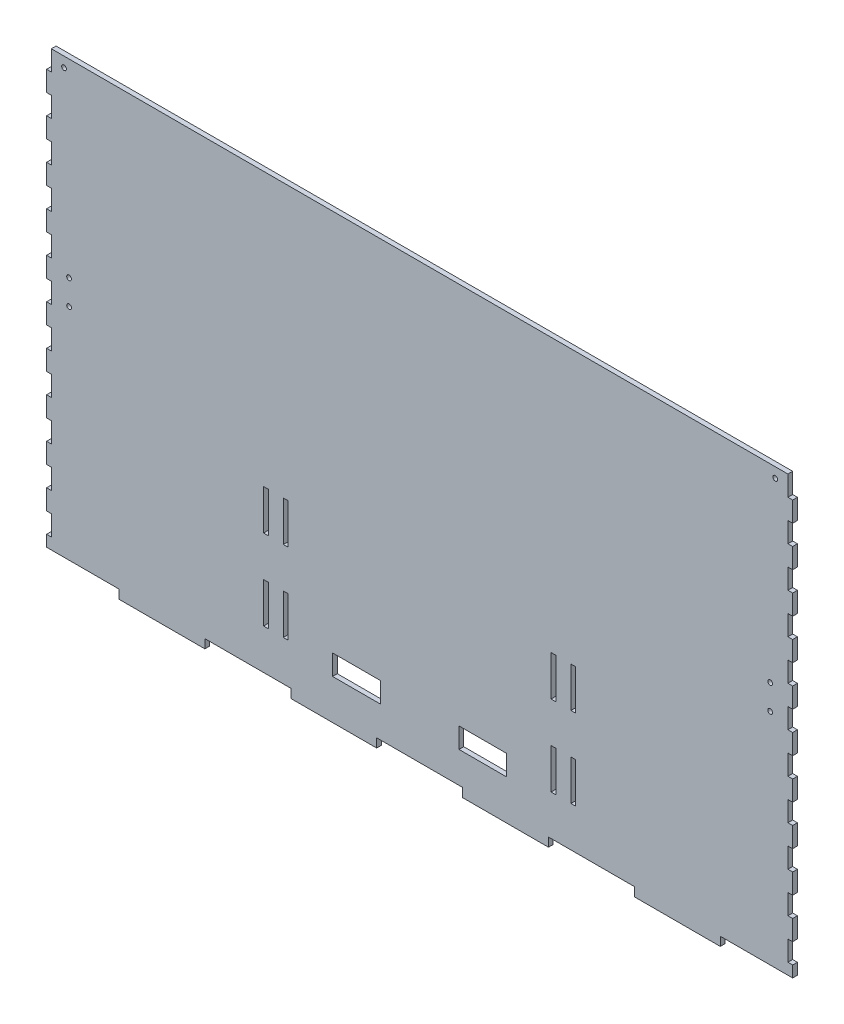
SolidWorks part; units mm, degrees
ref_plane "Front Plane" through (0, 0, 0) normal (0, 0, 1) x (1, 0, 0)
ref_plane "Top Plane" through (0, 0, 0) normal (0, 1, 0) x (1, 0, 0)
ref_plane "Right Plane" through (0, 0, 0) normal (1, 0, 0) x (0, 0, -1)
sketch "Sketch1" plane through (0, 0, 0) normal (0, 0, 1) x (1, 0, 0)
  line L0 (0, 139.7) -> (0, -139.7) construction
  line L1 (-406.4, 139.7) -> (406.4, 139.7)
  line L2 (-406.4, 139.7) -> (-406.4, -139.7)
  line L3 (-406.4, -139.7) -> (406.4, -139.7)
  line L4 (406.4, 139.7) -> (406.4, -139.7)
  line L49 (-380.8222, 127) -> (-380.8222, 114.3)
  line L54 (-380.8222, 139.7) -> (-377.825, 139.7)
  line L55 (-380.8222, 139.7) -> (-380.8222, 127)
  line L56 (-380.8222, 127) -> (-377.825, 127)
  line L57 (-377.825, 139.7) -> (-377.825, 127)
  line L58 (-380.8222, 127) -> (-377.825, 127)
  line L59 (-377.825, 127) -> (-377.825, 114.3)
  line L60 (-380.8222, 114.3) -> (-377.825, 114.3)
  line L61 (-380.8222, 114.3) -> (-380.8222, 101.6)
  line L62 (-380.8222, 114.3) -> (-377.825, 114.3)
  line L63 (-377.825, 114.3) -> (-377.825, 101.6)
  line L64 (-380.8222, 101.6) -> (-377.825, 101.6)
  line L65 (-380.8222, 101.6) -> (-380.8222, 88.9)
  line L66 (-380.8222, 101.6) -> (-377.825, 101.6)
  line L67 (-377.825, 101.6) -> (-377.825, 88.9)
  line L68 (-380.8222, 88.9) -> (-377.825, 88.9)
  line L69 (-380.8222, 88.9) -> (-380.8222, 76.2)
  line L70 (-380.8222, 88.9) -> (-377.825, 88.9)
  line L71 (-377.825, 88.9) -> (-377.825, 76.2)
  line L72 (-380.8222, 76.2) -> (-377.825, 76.2)
  line L73 (-380.8222, 76.2) -> (-380.8222, 63.5)
  line L74 (-380.8222, 76.2) -> (-377.825, 76.2)
  line L75 (-377.825, 76.2) -> (-377.825, 63.5)
  line L76 (-380.8222, 63.5) -> (-377.825, 63.5)
  line L77 (-380.8222, 63.5) -> (-380.8222, 50.8)
  line L78 (-380.8222, 63.5) -> (-377.825, 63.5)
  line L79 (-377.825, 63.5) -> (-377.825, 50.8)
  line L80 (-380.8222, 50.8) -> (-377.825, 50.8)
  line L81 (-380.8222, 50.8) -> (-380.8222, 38.1)
  line L82 (-380.8222, 50.8) -> (-377.825, 50.8)
  line L83 (-377.825, 50.8) -> (-377.825, 38.1)
  line L84 (-380.8222, 38.1) -> (-377.825, 38.1)
  line L85 (-380.8222, 38.1) -> (-380.8222, 25.4)
  line L86 (-380.8222, 38.1) -> (-377.825, 38.1)
  line L87 (-377.825, 38.1) -> (-377.825, 25.4)
  line L88 (-380.8222, 25.4) -> (-377.825, 25.4)
  line L89 (377.825, 127) -> (377.825, 114.3)
  line L90 (377.825, 139.7) -> (380.8222, 139.7)
  line L91 (377.825, 139.7) -> (377.825, 127)
  line L92 (377.825, 127) -> (380.8222, 127)
  line L93 (380.8222, 139.7) -> (380.8222, 127)
  line L94 (377.825, 127) -> (380.8222, 127)
  line L95 (380.8222, 127) -> (380.8222, 114.3)
  line L96 (377.825, 114.3) -> (380.8222, 114.3)
  line L97 (377.825, 114.3) -> (377.825, 101.6)
  line L98 (377.825, 114.3) -> (380.8222, 114.3)
  line L99 (380.8222, 114.3) -> (380.8222, 101.6)
  line L100 (377.825, 101.6) -> (380.8222, 101.6)
  line L101 (377.825, 101.6) -> (377.825, 88.9)
  line L102 (377.825, 101.6) -> (380.8222, 101.6)
  line L103 (380.8222, 101.6) -> (380.8222, 88.9)
  line L104 (377.825, 88.9) -> (380.8222, 88.9)
  line L105 (377.825, 88.9) -> (377.825, 76.2)
  line L106 (377.825, 88.9) -> (380.8222, 88.9)
  line L107 (380.8222, 88.9) -> (380.8222, 76.2)
  line L108 (377.825, 76.2) -> (380.8222, 76.2)
  line L109 (377.825, 76.2) -> (377.825, 63.5)
  line L110 (377.825, 76.2) -> (380.8222, 76.2)
  line L111 (380.8222, 76.2) -> (380.8222, 63.5)
  line L112 (377.825, 63.5) -> (380.8222, 63.5)
  line L113 (377.825, 63.5) -> (377.825, 50.8)
  line L114 (377.825, 63.5) -> (380.8222, 63.5)
  line L115 (380.8222, 63.5) -> (380.8222, 50.8)
  line L116 (377.825, 50.8) -> (380.8222, 50.8)
  line L117 (377.825, 50.8) -> (377.825, 38.1)
  line L118 (377.825, 50.8) -> (380.8222, 50.8)
  line L119 (380.8222, 50.8) -> (380.8222, 38.1)
  line L120 (377.825, 38.1) -> (380.8222, 38.1)
  line L121 (377.825, 38.1) -> (377.825, 25.4)
  line L122 (377.825, 38.1) -> (380.8222, 38.1)
  line L123 (380.8222, 38.1) -> (380.8222, 25.4)
  line L124 (377.825, 25.4) -> (380.8222, 25.4)
  line L125 (-352.2133, -134.112) -> (-352.2133, -139.7)
  line L126 (-406.4, -134.112) -> (-352.2133, -134.112)
  line L127 (-406.4, -134.112) -> (-406.4, -139.7)
  line L128 (-406.4, -139.7) -> (-352.2133, -139.7)
  line L129 (-352.2133, -134.112) -> (-352.2133, -139.7)
  line L130 (-352.2133, -134.112) -> (-298.0267, -134.112)
  line L131 (-298.0267, -134.112) -> (-298.0267, -139.7)
  line L132 (-352.2133, -139.7) -> (-298.0267, -139.7)
  line L133 (-298.0267, -134.112) -> (-298.0267, -139.7)
  line L134 (-298.0267, -134.112) -> (-243.84, -134.112)
  line L135 (-243.84, -134.112) -> (-243.84, -139.7)
  line L136 (-298.0267, -139.7) -> (-243.84, -139.7)
  line L137 (-243.84, -134.112) -> (-243.84, -139.7)
  line L138 (-243.84, -134.112) -> (-189.6533, -134.112)
  line L139 (-189.6533, -134.112) -> (-189.6533, -139.7)
  line L140 (-243.84, -139.7) -> (-189.6533, -139.7)
  line L141 (-189.6533, -134.112) -> (-189.6533, -139.7)
  line L142 (-189.6533, -134.112) -> (-135.4667, -134.112)
  line L143 (-135.4667, -134.112) -> (-135.4667, -139.7)
  line L144 (-189.6533, -139.7) -> (-135.4667, -139.7)
  line L145 (-135.4667, -134.112) -> (-135.4667, -139.7)
  line L146 (-135.4667, -134.112) -> (-81.28, -134.112)
  line L147 (-81.28, -134.112) -> (-81.28, -139.7)
  line L148 (-135.4667, -139.7) -> (-81.28, -139.7)
  line L149 (-81.28, -134.112) -> (-81.28, -139.7)
  line L150 (-81.28, -134.112) -> (-27.0933, -134.112)
  line L151 (-27.0933, -134.112) -> (-27.0933, -139.7)
  line L152 (-81.28, -139.7) -> (-27.0933, -139.7)
  line L153 (-27.0933, -134.112) -> (-27.0933, -139.7)
  line L154 (-27.0933, -134.112) -> (27.0933, -134.112)
  line L155 (27.0933, -134.112) -> (27.0933, -139.7)
  line L156 (-27.0933, -139.7) -> (27.0933, -139.7)
  line L157 (27.0933, -134.112) -> (27.0933, -139.7)
  line L158 (27.0933, -134.112) -> (81.28, -134.112)
  line L159 (81.28, -134.112) -> (81.28, -139.7)
  line L160 (27.0933, -139.7) -> (81.28, -139.7)
  line L161 (81.28, -134.112) -> (81.28, -139.7)
  line L162 (81.28, -134.112) -> (135.4667, -134.112)
  line L163 (135.4667, -134.112) -> (135.4667, -139.7)
  line L164 (81.28, -139.7) -> (135.4667, -139.7)
  line L165 (135.4667, -134.112) -> (135.4667, -139.7)
  line L166 (135.4667, -134.112) -> (189.6533, -134.112)
  line L167 (189.6533, -134.112) -> (189.6533, -139.7)
  line L168 (135.4667, -139.7) -> (189.6533, -139.7)
  line L169 (189.6533, -134.112) -> (189.6533, -139.7)
  line L170 (189.6533, -134.112) -> (243.84, -134.112)
  line L171 (243.84, -134.112) -> (243.84, -139.7)
  line L172 (189.6533, -139.7) -> (243.84, -139.7)
  line L173 (243.84, -134.112) -> (243.84, -139.7)
  line L174 (243.84, -134.112) -> (298.0267, -134.112)
  line L175 (298.0267, -134.112) -> (298.0267, -139.7)
  line L176 (243.84, -139.7) -> (298.0267, -139.7)
  line L177 (298.0267, -134.112) -> (298.0267, -139.7)
  line L178 (298.0267, -134.112) -> (352.2133, -134.112)
  line L179 (352.2133, -134.112) -> (352.2133, -139.7)
  line L180 (298.0267, -139.7) -> (352.2133, -139.7)
  line L181 (352.2133, -134.112) -> (352.2133, -139.7)
  line L182 (352.2133, -134.112) -> (406.4, -134.112)
  line L183 (406.4, -134.112) -> (406.4, -139.7)
  line L184 (352.2133, -139.7) -> (406.4, -139.7)
  line L205 (-90.678, 84.5227) -> (-90.678, -139.7) construction
  line L206 (90.678, 84.5227) -> (90.678, -139.7) construction
  line L207 (-90.678, -27.5886) -> (90.678, -27.5886) construction
  line L208 (-380.8222, 25.4) -> (-380.8222, 12.7)
  line L209 (-380.8222, 25.4) -> (-377.825, 25.4)
  line L210 (-377.825, 25.4) -> (-377.825, 12.7)
  line L211 (-380.8222, 12.7) -> (-377.825, 12.7)
  line L212 (-380.8222, 12.7) -> (-380.8222, 0)
  line L213 (-380.8222, 12.7) -> (-377.825, 12.7)
  line L214 (-377.825, 12.7) -> (-377.825, 0)
  line L215 (-380.8222, 0) -> (-377.825, 0)
  line L224 (-377.825, 0) -> (377.825, 0) construction
  line L229 (377.825, 25.4) -> (377.825, 12.7)
  line L230 (377.825, 25.4) -> (380.8222, 25.4)
  line L231 (380.8222, 25.4) -> (380.8222, 12.7)
  line L232 (377.825, 12.7) -> (380.8222, 12.7)
  line L233 (377.825, 12.7) -> (377.825, 0)
  line L234 (377.825, 12.7) -> (380.8222, 12.7)
  line L235 (380.8222, 12.7) -> (380.8222, 0)
  line L236 (377.825, 0) -> (380.8222, 0)
  line L237 (-380.8222, 0) -> (-380.8222, -12.7)
  line L238 (-380.8222, 0) -> (-377.825, 0)
  line L239 (-377.825, 0) -> (-377.825, -12.7)
  line L240 (-380.8222, -12.7) -> (-377.825, -12.7)
  line L241 (-380.8222, -12.7) -> (-380.8222, -25.4)
  line L242 (-380.8222, -12.7) -> (-377.825, -12.7)
  line L243 (-377.825, -12.7) -> (-377.825, -25.4)
  line L244 (-380.8222, -25.4) -> (-377.825, -25.4)
  line L245 (-380.8222, -25.4) -> (-380.8222, -38.1)
  line L246 (-380.8222, -25.4) -> (-377.825, -25.4)
  line L247 (-377.825, -25.4) -> (-377.825, -38.1)
  line L248 (-380.8222, -38.1) -> (-377.825, -38.1)
  line L249 (-380.8222, -38.1) -> (-380.8222, -50.8)
  line L250 (-380.8222, -38.1) -> (-377.825, -38.1)
  line L251 (-377.825, -38.1) -> (-377.825, -50.8)
  line L252 (-380.8222, -50.8) -> (-377.825, -50.8)
  line L253 (-380.8222, -50.8) -> (-380.8222, -63.5)
  line L254 (-380.8222, -50.8) -> (-377.825, -50.8)
  line L255 (-377.825, -50.8) -> (-377.825, -63.5)
  line L256 (-380.8222, -63.5) -> (-377.825, -63.5)
  line L257 (-380.8222, -63.5) -> (-380.8222, -76.2)
  line L258 (-380.8222, -63.5) -> (-377.825, -63.5)
  line L259 (-377.825, -63.5) -> (-377.825, -76.2)
  line L260 (-380.8222, -76.2) -> (-377.825, -76.2)
  line L261 (-380.8222, -76.2) -> (-380.8222, -88.9)
  line L262 (-380.8222, -76.2) -> (-377.825, -76.2)
  line L263 (-377.825, -76.2) -> (-377.825, -88.9)
  line L264 (-380.8222, -88.9) -> (-377.825, -88.9)
  line L265 (-380.8222, -88.9) -> (-380.8222, -101.6)
  line L266 (-380.8222, -88.9) -> (-377.825, -88.9)
  line L267 (-377.825, -88.9) -> (-377.825, -101.6)
  line L268 (-380.8222, -101.6) -> (-377.825, -101.6)
  line L269 (-380.8222, -101.6) -> (-380.8222, -114.3)
  line L270 (-380.8222, -101.6) -> (-377.825, -101.6)
  line L271 (-377.825, -101.6) -> (-377.825, -114.3)
  line L272 (-380.8222, -114.3) -> (-377.825, -114.3)
  line L273 (-380.8222, -114.3) -> (-380.8222, -127)
  line L274 (-380.8222, -114.3) -> (-377.825, -114.3)
  line L275 (-377.825, -114.3) -> (-377.825, -127)
  line L276 (-380.8222, -127) -> (-377.825, -127)
  line L277 (-380.8222, -127) -> (-380.8222, -139.7)
  line L278 (-380.8222, -127) -> (-377.825, -127)
  line L279 (-377.825, -127) -> (-377.825, -139.7)
  line L280 (-380.8222, -139.7) -> (-377.825, -139.7)
  line L281 (377.825, 0) -> (377.825, -12.7)
  line L282 (377.825, 0) -> (380.8222, 0)
  line L283 (380.8222, 0) -> (380.8222, -12.7)
  line L284 (377.825, -12.7) -> (380.8222, -12.7)
  line L285 (377.825, -12.7) -> (377.825, -25.4)
  line L286 (377.825, -12.7) -> (380.8222, -12.7)
  line L287 (380.8222, -12.7) -> (380.8222, -25.4)
  line L288 (377.825, -25.4) -> (380.8222, -25.4)
  line L289 (377.825, -25.4) -> (377.825, -38.1)
  line L290 (377.825, -25.4) -> (380.8222, -25.4)
  line L291 (380.8222, -25.4) -> (380.8222, -38.1)
  line L292 (377.825, -38.1) -> (380.8222, -38.1)
  line L293 (377.825, -38.1) -> (377.825, -50.8)
  line L294 (377.825, -38.1) -> (380.8222, -38.1)
  line L295 (380.8222, -38.1) -> (380.8222, -50.8)
  line L296 (377.825, -50.8) -> (380.8222, -50.8)
  line L297 (377.825, -50.8) -> (377.825, -63.5)
  line L298 (377.825, -50.8) -> (380.8222, -50.8)
  line L299 (380.8222, -50.8) -> (380.8222, -63.5)
  line L300 (377.825, -63.5) -> (380.8222, -63.5)
  line L301 (377.825, -63.5) -> (377.825, -76.2)
  line L302 (377.825, -63.5) -> (380.8222, -63.5)
  line L303 (380.8222, -63.5) -> (380.8222, -76.2)
  line L304 (377.825, -76.2) -> (380.8222, -76.2)
  line L305 (377.825, -76.2) -> (377.825, -88.9)
  line L306 (377.825, -76.2) -> (380.8222, -76.2)
  line L307 (380.8222, -76.2) -> (380.8222, -88.9)
  line L308 (377.825, -88.9) -> (380.8222, -88.9)
  line L309 (377.825, -88.9) -> (377.825, -101.6)
  line L310 (377.825, -88.9) -> (380.8222, -88.9)
  line L311 (380.8222, -88.9) -> (380.8222, -101.6)
  line L312 (377.825, -101.6) -> (380.8222, -101.6)
  line L313 (377.825, -101.6) -> (377.825, -114.3)
  line L314 (377.825, -101.6) -> (380.8222, -101.6)
  line L315 (380.8222, -101.6) -> (380.8222, -114.3)
  line L316 (377.825, -114.3) -> (380.8222, -114.3)
  line L317 (377.825, -114.3) -> (377.825, -127)
  line L318 (377.825, -114.3) -> (380.8222, -114.3)
  line L319 (380.8222, -114.3) -> (380.8222, -127)
  line L320 (377.825, -127) -> (380.8222, -127)
  line L321 (377.825, -127) -> (377.825, -139.7)
  line L322 (377.825, -127) -> (380.8222, -127)
  line L323 (380.8222, -127) -> (380.8222, -139.7)
  line L324 (377.825, -139.7) -> (380.8222, -139.7)
  point P6 (0, 0)
  point P128 (0, -27.5886)
  point P153 (0, 0)
  dimension "D4" = 12.7
  dimension "D5" = 2.9972
  dimension "D10" = 181.356
  dimension "D12" = 755.65
  dimension "D8" = 812.8
  dimension "D11" = 54.1867
  dimension "D2" = 273.812
  dimension "D9" = 279.4
  dimension "D3" = 22
  dimension "D7" = 15
  dimension "D6" = 22
extrude "Main Extrude" add sketch "Sketch1" along normal blind 2.9972 contours L321 L317 L313 L309 L305 L301 L297 L293 L289 L285 L281 L233 L229 L121 L117 L113 L109 L105 L101 L97 L89 L91 L1 L57 L59 L63 L67 L71 L75 L79 L83 L87 L210 L214 L239 L243 L247 L251 L255 L259 L263 L267 L271 L275 L279 L126 L130 L134 L138 L142 L146 | L277 L273 L269 L265 L261 L257 L253 L249 L245 L241 L237 L212 L208 L85 L81 L77 L73 L69 L65 L61 L49 L55 L1 L2 L126 | L319 L323 L182 L4 L1 L93 L95 L99 L103 L107 L111 L115 L119 L123 L231 L235 L283 L287 L291 L295 L299 L303 L307 L311 L315 | L126 L279 L3 L125 | L135 L134 L131 L3 | L143 L142 L139 L3 | L151 L150 L147 L3 | L159 L158 L155 L3 | L167 L166 L163 L3 | L175 L174 L171 L3 | L323 L182 L321 L184 | L89 L96 L95 L92 | L101 L104 L103 L100 | L109 L112 L111 L108 | L117 L120 L119 L116 | L229 L232 L231 L124 | L281 L284 L283 L236 | L289 L292 L291 L288 | L297 L300 L299 L296 | L305 L308 L307 L304 | L313 L316 L315 L312 | L323 L320 L321 L182 | L49 L60 L59 L56 | L65 L68 L67 L64 | L73 L76 L75 L72 | L81 L84 L83 L80 | L208 L211 L210 L88 | L237 L240 L239 L215 | L245 L248 L247 L244 | L253 L256 L255 L252 | L261 L264 L263 L260 | L269 L272 L271 L268 | L279 L276 L277 L126 | L277 L126 L2 L3 | L321 L182 L179 L3 | L182 L323 L3 L4 | L279 L126 L277 L128 region at (-393.6111, 2.794, 0) region at (-393.6111, -136.906, 0) region at (0, 2.794, 0) region at (-379.3236, 120.65, 0) region at (-379.3236, -130.556, 0) region at (-379.3236, -136.906, 0) region at (-365.0192, -136.906, 0) region at (393.6111, 2.794, 0) region at (379.3236, 120.65, 0) region at (-379.3236, 95.25, 0) region at (-379.3236, -107.95, 0) region at (-270.9333, -136.906, 0) region at (393.6111, -136.906, 0) region at (379.3236, 95.25, 0) region at (-379.3236, 69.85, 0) region at (-379.3236, -82.55, 0) region at (379.3236, -136.906, 0) region at (379.3236, -130.556, 0) region at (-162.56, -136.906, 0) region at (365.0192, -136.906, 0) region at (379.3236, 69.85, 0) region at (-379.3236, 44.45, 0) region at (-379.3236, -57.15, 0) region at (379.3236, -107.95, 0) region at (-54.1867, -136.906, 0) region at (270.9333, -136.906, 0) region at (379.3236, 44.45, 0) region at (-379.3236, 19.05, 0) region at (-379.3236, -31.75, 0) region at (379.3236, -82.55, 0) region at (54.1867, -136.906, 0) region at (162.56, -136.906, 0) region at (379.3236, 19.05, 0) region at (-379.3236, -6.35, 0) region at (379.3236, -57.15, 0) region at (379.3236, -6.35, 0) region at (379.3236, -31.75, 0)
sketch "Sketch8" plane through (0, 0, 2.9972) normal (0, 0, 1) x (1, 0, 0)
  line L0 (-406.4, 139.7) -> (-406.4, -139.7) construction
  line L1 (-380.8222, 28.2575) -> (-383.9972, 28.2575)
  line L2 (-380.8222, 28.2575) -> (-380.8222, -3.6195)
  line L3 (-380.8222, -3.6195) -> (-383.9972, -3.6195)
  line L4 (-383.9972, 28.2575) -> (-383.9972, -3.6195)
  line L5 (-406.4, -139.7) -> (-352.2133, -139.7) construction
  line L6 (380.8222, 28.2575) -> (383.9972, 28.2575)
  line L7 (380.8222, 28.2575) -> (380.8222, -3.6195)
  line L8 (380.8222, -3.6195) -> (383.9972, -3.6195)
  line L9 (383.9972, 28.2575) -> (383.9972, -3.6195)
  line L11 (-380.8222, 88.9) -> (-380.8222, 76.2) construction
  line L12 (-352.2133, -134.112) -> (-298.0267, -134.112) construction
  line L13 (380.8222, 88.9) -> (380.8222, 76.2) construction
  line L14 (-393.7, -120.65) -> (393.7, -120.65) construction
  circle A0 centre (-393.7, -120.65) radius 1.5
  circle A1 centre (393.7, -120.65) radius 1.5
  point P6 (0, -120.65)
  point P16 (-383.9972, 12.319)
  dimension "D5" = 3
  dimension "D1" = 31.877
  dimension "D2" = 3.175
  dimension "D3" = 146.431
  dimension "D4" = 19.05
  dimension "D6" = 12.7
extrude "Mount Holes" cut sketch "Sketch8" against normal through all
sketch "Sketch3" plane through (0, 0, 2.9972) normal (0, 0, 1) x (1, 0, 0)
  line L0 (-135.4667, -134.112) -> (-81.28, -134.112) construction
  line L1 (-95.4278, 126.492) -> (-85.9282, 126.492)
  line L2 (-95.4278, 126.492) -> (-95.4278, -134.112)
  line L3 (-95.4278, -134.112) -> (-85.9282, -134.112)
  line L4 (-85.9282, 126.492) -> (-85.9282, -134.112)
  line L5 (81.28, -134.112) -> (135.4667, -134.112) construction
  line L6 (85.9282, 126.492) -> (95.4278, 126.492)
  line L7 (85.9282, 126.492) -> (85.9282, -134.112)
  line L8 (85.9282, -134.112) -> (95.4278, -134.112)
  line L9 (95.4278, 126.492) -> (95.4278, -134.112)
  line L10 (-85.9282, -3.81) -> (85.9282, -3.81) construction
  line L12 (-103.378, 10.3505) -> (-77.978, 10.3505)
  line L13 (-103.378, 10.3505) -> (-103.378, 0.8255)
  line L14 (-103.378, 0.8255) -> (-77.978, 0.8255)
  line L15 (-77.978, 10.3505) -> (-77.978, 0.8255)
  line L16 (77.978, 10.3505) -> (103.378, 10.3505)
  line L17 (77.978, 10.3505) -> (77.978, 0.8255)
  line L18 (77.978, 0.8255) -> (103.378, 0.8255)
  line L19 (103.378, 10.3505) -> (103.378, 0.8255)
  point P14 (-90.678, 126.492)
  point P15 (90.678, 126.492)
  point P16 (0, -3.81)
  point P27 (-90.678, 10.3505)
  point P28 (90.678, 10.3505)
  point P29 (-77.978, 5.588)
  dimension "D1" = 9.4996
  dimension "D2" = 260.604
  dimension "D3" = 181.356
  dimension "D4" = 9.525
  dimension "D5" = 139.7
  dimension "D6" = 25.4
extrude "Door Slots" [suppressed] cut sketch "Sketch3" against normal through all contours L2 L12 L4 L1 | L2 L14 L4 L12 | L15 L12 L4 L14 | L13 L14 L2 L12 | L14 L2 L3 L4 | L7 L16 L9 L6 | L7 L18 L9 L16 | L19 L16 L9 L18 | L17 L18 L7 L16 | L18 L7 L8 L9
sketch "Sketch4" plane through (0, 0, 0) normal (0, 0, 1) x (1, 0, 0)
  line L1 (-81.28, -139.7) -> (-27.0933, -139.7) construction
  line L2 (-61.9252, -112.522) -> (-58.928, -112.522)
  line L3 (-58.928, -112.522) -> (-58.928, -106.172)
  line L4 (-58.928, -106.172) -> (-8.128, -106.172)
  line L5 (-8.128, -106.172) -> (-8.128, -112.522)
  line L6 (-8.128, -112.522) -> (-5.1308, -112.522)
  line L9 (-61.9252, -112.522) -> (-61.9252, -134.112)
  line L10 (-61.9252, -134.112) -> (-58.928, -134.112)
  line L11 (-58.928, -134.112) -> (-58.928, -139.7)
  line L12 (-5.1308, -112.522) -> (-5.1308, -134.112)
  line L13 (-5.1308, -134.112) -> (-8.128, -134.112)
  line L14 (-8.128, -134.112) -> (-8.128, -139.7)
  line L15 (-58.928, -139.7) -> (-8.128, -139.7)
  line L16 (-27.0933, -134.112) -> (27.0933, -134.112) construction
  line L17 (-27.0933, -134.112) -> (27.0933, -134.112) construction
  line L18 (12.128, -101.642) -> (42.228, -101.642)
  line L19 (12.128, -101.642) -> (12.128, -114.492)
  line L20 (12.128, -114.492) -> (42.228, -114.492)
  line L21 (42.228, -101.642) -> (42.228, -114.492)
  line L24 (-95.4278, -134.112) -> (-85.9282, -134.112) construction
  line L25 (85.9282, -134.112) -> (95.4278, -134.112) construction
  point P9 (-33.528, -106.172)
  point P10 (-33.528, -139.7)
  point P22 (27.178, -114.492)
  point P25 (90.678, -134.112)
  point P26 (12.128, -108.067)
  point P30 (-90.678, -134.112)
  dimension "D1" = 50.8
  dimension "D2" = 2.9972
  dimension "D4" = 21.59
  dimension "D5" = 30.1
  dimension "D6" = 12.85
  dimension "D9" = 57.15
  dimension "D8" = 63.5
  dimension "D3" = 27.94
  dimension "D7" = 26.045
extrude "Trough and Lever Holes" [suppressed] cut sketch "Sketch4" along normal through all contours L11 L15 L14 L13 L12 L6 L5 L4 L3 L2 L9 L10 | L21 L18 L19 L20
sketch "Sketch5" plane through (0, 0, 2.9972) normal (0, 0, 1) x (1, 0, 0)
  line L0 (-90.678, 126.492) -> (-90.678, -134.112) construction
  line L1 (-95.4278, 126.492) -> (-85.9282, 126.492) construction
  line L2 (-95.4278, -134.112) -> (-85.9282, -134.112) construction
  line L3 (90.678, 126.492) -> (90.678, -134.112) construction
  line L4 (85.9282, 126.492) -> (95.4278, 126.492) construction
  line L5 (85.9282, -134.112) -> (95.4278, -134.112) construction
  line L6 (-135.4667, -134.112) -> (-81.28, -134.112) construction
  line L19 (-98.425, -134.112) -> (-95.4278, -134.112)
  line L20 (-98.425, -134.112) -> (-98.425, -108.712)
  line L21 (-98.425, -108.712) -> (-95.4278, -108.712)
  line L22 (-95.4278, -134.112) -> (-95.4278, -108.712)
  line L24 (-98.425, -108.712) -> (-95.4278, -108.712)
  line L25 (-98.425, -108.712) -> (-98.425, -83.312)
  line L26 (-98.425, -83.312) -> (-95.4278, -83.312)
  line L27 (-95.4278, -108.712) -> (-95.4278, -83.312)
  line L28 (-95.4278, -83.312) -> (-98.425, -83.312)
  line L29 (-95.4278, -83.312) -> (-95.4278, -57.912)
  line L30 (-95.4278, -57.912) -> (-98.425, -57.912)
  line L31 (-98.425, -83.312) -> (-98.425, -57.912)
  line L32 (-98.425, -57.912) -> (-95.4278, -57.912)
  line L33 (-98.425, -57.912) -> (-98.425, -32.512)
  line L34 (-98.425, -32.512) -> (-95.4278, -32.512)
  line L35 (-95.4278, -57.912) -> (-95.4278, -32.512)
  line L36 (-95.4278, -32.512) -> (-98.425, -32.512)
  line L37 (-95.4278, -32.512) -> (-95.4278, -7.112)
  line L38 (-95.4278, -7.112) -> (-98.425, -7.112)
  line L39 (-98.425, -32.512) -> (-98.425, -7.112)
  line L40 (-82.931, -108.712) -> (-85.9282, -108.712)
  line L41 (-85.9282, -134.112) -> (-85.9282, -108.712)
  line L42 (-82.931, -134.112) -> (-85.9282, -134.112)
  line L43 (-82.931, -134.112) -> (-82.931, -108.712)
  line L44 (-82.931, -83.312) -> (-85.9282, -83.312)
  line L45 (-85.9282, -108.712) -> (-85.9282, -83.312)
  line L46 (-82.931, -108.712) -> (-85.9282, -108.712)
  line L47 (-82.931, -108.712) -> (-82.931, -83.312)
  line L48 (-85.9282, -57.912) -> (-82.931, -57.912)
  line L49 (-82.931, -83.312) -> (-82.931, -57.912)
  line L50 (-85.9282, -83.312) -> (-82.931, -83.312)
  line L51 (-85.9282, -83.312) -> (-85.9282, -57.912)
  line L52 (-82.931, -32.512) -> (-85.9282, -32.512)
  line L53 (-85.9282, -57.912) -> (-85.9282, -32.512)
  line L54 (-82.931, -57.912) -> (-85.9282, -57.912)
  line L55 (-82.931, -57.912) -> (-82.931, -32.512)
  line L56 (-85.9282, -7.112) -> (-82.931, -7.112)
  line L57 (-82.931, -32.512) -> (-82.931, -7.112)
  line L58 (-85.9282, -32.512) -> (-82.931, -32.512)
  line L59 (-85.9282, -32.512) -> (-85.9282, -7.112)
  line L60 (0, -1.6485) -> (0, 1.6485) construction
  line L61 (98.425, -108.712) -> (95.4278, -108.712)
  line L62 (95.4278, -134.112) -> (95.4278, -108.712)
  line L63 (98.425, -134.112) -> (95.4278, -134.112)
  line L64 (98.425, -134.112) -> (98.425, -108.712)
  line L65 (98.425, -83.312) -> (95.4278, -83.312)
  line L66 (95.4278, -108.712) -> (95.4278, -83.312)
  line L67 (98.425, -108.712) -> (95.4278, -108.712)
  line L68 (98.425, -108.712) -> (98.425, -83.312)
  line L69 (95.4278, -57.912) -> (98.425, -57.912)
  line L70 (98.425, -83.312) -> (98.425, -57.912)
  line L71 (95.4278, -83.312) -> (98.425, -83.312)
  line L72 (95.4278, -83.312) -> (95.4278, -57.912)
  line L73 (98.425, -32.512) -> (95.4278, -32.512)
  line L74 (95.4278, -57.912) -> (95.4278, -32.512)
  line L75 (98.425, -57.912) -> (95.4278, -57.912)
  line L76 (98.425, -57.912) -> (98.425, -32.512)
  line L77 (95.4278, -7.112) -> (98.425, -7.112)
  line L78 (98.425, -32.512) -> (98.425, -7.112)
  line L79 (95.4278, -32.512) -> (98.425, -32.512)
  line L80 (95.4278, -32.512) -> (95.4278, -7.112)
  line L81 (85.9282, -32.512) -> (85.9282, -7.112)
  line L82 (85.9282, -32.512) -> (82.931, -32.512)
  line L83 (82.931, -32.512) -> (82.931, -7.112)
  line L84 (85.9282, -7.112) -> (82.931, -7.112)
  line L85 (82.931, -57.912) -> (82.931, -32.512)
  line L86 (82.931, -57.912) -> (85.9282, -57.912)
  line L87 (85.9282, -57.912) -> (85.9282, -32.512)
  line L88 (82.931, -32.512) -> (85.9282, -32.512)
  line L89 (85.9282, -83.312) -> (85.9282, -57.912)
  line L90 (85.9282, -83.312) -> (82.931, -83.312)
  line L91 (82.931, -83.312) -> (82.931, -57.912)
  line L92 (85.9282, -57.912) -> (82.931, -57.912)
  line L93 (82.931, -108.712) -> (82.931, -83.312)
  line L94 (82.931, -108.712) -> (85.9282, -108.712)
  line L95 (85.9282, -108.712) -> (85.9282, -83.312)
  line L96 (82.931, -83.312) -> (85.9282, -83.312)
  line L97 (82.931, -134.112) -> (82.931, -108.712)
  line L98 (82.931, -134.112) -> (85.9282, -134.112)
  line L99 (85.9282, -134.112) -> (85.9282, -108.712)
  line L100 (82.931, -108.712) -> (85.9282, -108.712)
  dimension "D2" = 2.9972
  dimension "D1" = 25.4
  dimension "D3" = 4.7498
extrude "Door Guide Slots" cut sketch "Sketch5" against normal through all contours L21 L27 L26 L25 | L30 L35 L34 L33 | L48 L55 L52 L53 | L40 L47 L44 L45 | L86 L87 L82 L85 | L94 L95 L90 L93 | L69 L76 L73 L74 | L61 L68 L65 L66 region at (-96.9264, -96.012, 2.9972) region at (-96.9264, -45.212, 2.9972) region at (-84.4296, -96.012, 2.9972) region at (-84.4296, -45.212, 2.9972) region at (96.9264, -96.012, 2.9972) region at (96.9264, -45.212, 2.9972) region at (84.4296, -45.212, 2.9972) region at (84.4296, -96.012, 2.9972)
sketch "Sketch7" plane through (0, 0, 2.9972) normal (0, 0, 1) x (1, 0, 0)
  line L0 (-24.828, -108.067) -> (24.828, -108.067) construction
  line L1 (-54.928, -101.642) -> (-24.828, -101.642)
  line L2 (-54.928, -101.642) -> (-54.928, -114.492)
  line L3 (-54.928, -114.492) -> (-24.828, -114.492)
  line L4 (-24.828, -101.642) -> (-24.828, -114.492)
  line L5 (54.928, -101.642) -> (24.828, -101.642)
  line L6 (54.928, -101.642) -> (54.928, -114.492)
  line L7 (54.928, -114.492) -> (24.828, -114.492)
  line L8 (24.828, -101.642) -> (24.828, -114.492)
  line L9 (0, -108.067) -> (0, 0) construction
  line L10 (-95.4278, -134.112) -> (-85.9282, -134.112) construction
  line L12 (-135.4667, -134.112) -> (-81.28, -134.112) construction
  point P12 (-54.928, -108.067)
  point P15 (-39.878, -101.642)
  point P18 (-90.678, -134.112)
  dimension "D1" = 12.85
  dimension "D2" = 30.1
  dimension "D3" = 50.8
  dimension "D4" = 26.045
extrude "Lever Holes" cut sketch "Sketch7" against normal through all
sketch "Sketch9" [suppressed] plane through (0, 0, 2.9972) normal (0, 0, 1) x (1, 0, 0)
  line L0 (-79.9282, 116.038) -> (-79.9282, 110.938) construction
  line L1 (-78.4282, 116.038) -> (-78.4282, 110.938)
  line L2 (-81.4282, 116.038) -> (-81.4282, 110.938)
  line L3 (-79.9282, 46.038) -> (-79.9282, 40.938) construction
  line L4 (-78.4282, 46.038) -> (-78.4282, 40.938)
  line L5 (-81.4282, 46.038) -> (-81.4282, 40.938)
  line L6 (79.9282, 116.038) -> (79.9282, 110.938) construction
  line L7 (81.4282, 116.038) -> (81.4282, 110.938)
  line L8 (78.4282, 116.038) -> (78.4282, 110.938)
  line L9 (79.9282, 46.038) -> (79.9282, 40.938) construction
  line L10 (81.4282, 46.038) -> (81.4282, 40.938)
  line L11 (78.4282, 46.038) -> (78.4282, 40.938)
  line L12 (-85.9282, 126.492) -> (-85.9282, 10.3505) construction
  line L13 (-79.9282, 113.488) -> (79.9282, 113.488) construction
  line L14 (-95.4278, 126.492) -> (-85.9282, 126.492) construction
  line L15 (-79.9282, 113.488) -> (-79.9282, 43.488) construction
  arc A0 (-78.4282, 116.038) -> (-81.4282, 116.038) centre (-79.9282, 116.038) ccw
  arc A1 (-81.4282, 110.938) -> (-78.4282, 110.938) centre (-79.9282, 110.938) ccw
  arc A2 (-78.4282, 46.038) -> (-81.4282, 46.038) centre (-79.9282, 46.038) ccw
  arc A3 (-81.4282, 40.938) -> (-78.4282, 40.938) centre (-79.9282, 40.938) ccw
  arc A4 (81.4282, 116.038) -> (78.4282, 116.038) centre (79.9282, 116.038) ccw
  arc A5 (78.4282, 110.938) -> (81.4282, 110.938) centre (79.9282, 110.938) ccw
  arc A6 (81.4282, 46.038) -> (78.4282, 46.038) centre (79.9282, 46.038) ccw
  arc A7 (78.4282, 40.938) -> (81.4282, 40.938) centre (79.9282, 40.938) ccw
  point P2 (-79.9282, 113.488)
  point P7 (-79.9282, 43.488)
  point P14 (79.9282, 113.488)
  point P21 (79.9282, 43.488)
  point P30 (0, 113.488)
  point P31 (-79.9282, 88.138)
  dimension "D2" = 1.5
  dimension "D1" = 70
  dimension "D3" = 6
  dimension "D4" = 5.1
  dimension "D5" = 38.354
  dimension "D6" = 25.35
extrude "Door Servo Mount Holes" [suppressed] cut sketch "Sketch9" against normal through all
sketch "Sketch10" [suppressed] plane through (0, 0, 2.9972) normal (0, 0, 1) x (1, 0, 0)
  line L0 (-101.678, 127.492) -> (-79.678, 127.492) construction
  line L2 (-95.4278, 126.492) -> (-85.9282, 126.492) construction
  line L3 (-90.678, 127.492) -> (-90.678, 126.492) construction
  line L4 (79.678, 127.492) -> (101.678, 127.492) construction
  line L5 (90.678, 127.492) -> (90.678, 126.492) construction
  line L6 (85.9282, 126.492) -> (95.4278, 126.492) construction
  circle A0 centre (-101.678, 127.492) radius 1.5
  circle A1 centre (-79.678, 127.492) radius 1.5
  circle A2 centre (79.678, 127.492) radius 1.5
  circle A3 centre (101.678, 127.492) radius 1.5
  dimension "D1" = 3
  dimension "D2" = 22
  dimension "D3" = 1
extrude "Door Guide Mount Holes" [suppressed] cut sketch "Sketch10" against normal through all
sketch "Sketch12" plane through (0, 0, 2.9972) normal (0, 0, 1) x (1, 0, 0)
  line L0 (-246.507, 20.193) -> (-246.507, 4.445) construction
  line L1 (-221.107, 20.193) -> (-221.107, 4.445) construction
  line L2 (-246.507, 20.193) -> (-221.107, 20.193) construction
  line L3 (-246.507, 4.445) -> (-221.107, 4.445) construction
  line L4 (-243.332, 133.35) -> (-224.282, 133.35) construction
  line L5 (-406.4, 139.7) -> (406.4, 139.7) construction
  line L6 (-233.807, 20.193) -> (-233.807, 133.35) construction
  line L7 (-243.84, -134.112) -> (-189.6533, -134.112) construction
  line L8 (0, -1.6485) -> (0, 1.6485) construction
  line L9 (233.807, 20.193) -> (233.807, 133.35) construction
  line L10 (243.332, 133.35) -> (224.282, 133.35) construction
  line L11 (246.507, 4.445) -> (221.107, 4.445) construction
  line L12 (246.507, 20.193) -> (221.107, 20.193) construction
  line L13 (221.107, 20.193) -> (221.107, 4.445) construction
  line L14 (246.507, 20.193) -> (246.507, 4.445) construction
  circle A0 centre (-246.507, 20.193) radius 1.5
  circle A1 centre (-246.507, 4.445) radius 1.5
  circle A2 centre (-221.107, 4.445) radius 1.5
  circle A3 centre (-221.107, 20.193) radius 1.5
  circle A4 centre (-243.332, 133.35) radius 1.5
  circle A5 centre (-224.282, 133.35) radius 1.5
  circle A6 centre (224.282, 133.35) radius 1.5
  circle A7 centre (243.332, 133.35) radius 1.5
  circle A8 centre (221.107, 20.193) radius 1.5
  circle A9 centre (221.107, 4.445) radius 1.5
  circle A10 centre (246.507, 4.445) radius 1.5
  circle A11 centre (246.507, 20.193) radius 1.5
  point P12 (-233.807, 133.35)
  dimension "D1" = 3
  dimension "D2" = 233.807
  dimension "D3" = 19.05
  dimension "D4" = 6.35
  dimension "D5" = 25.4
  dimension "D6" = 15.748
  dimension "D7" = 138.557
extrude "Extension Clip Holes" cut sketch "Sketch12" against normal through all
sketch "Sketch11" plane through (0, 0, 2.9972) normal (0, 0, 1) x (1, 0, 0)
  line L0 (-232.3084, 139.7) -> (-232.3084, 127)
  line L1 (-232.3084, 127) -> (-235.3056, 127)
  line L2 (-235.3056, 127) -> (-235.3056, 114.3)
  line L3 (-235.3056, 114.3) -> (-232.3084, 114.3)
  line L4 (232.3084, 139.7) -> (232.3084, 127)
  line L5 (232.3084, 127) -> (235.3056, 127)
  line L6 (235.3056, 127) -> (235.3056, 114.3)
  line L7 (235.3056, 114.3) -> (232.3084, 114.3)
  line L9 (-380.8222, 127) -> (-377.825, 127) construction
  line L10 (-377.825, 139.7) -> (-377.825, 127) construction
  line L11 (235.3056, 120.65) -> (-235.3056, 120.65) construction
  line L12 (-232.3084, 114.3) -> (-232.3084, 101.6)
  line L13 (-232.3084, 101.6) -> (-235.3056, 101.6)
  line L14 (-235.3056, 101.6) -> (-235.3056, 88.9)
  line L15 (-235.3056, 88.9) -> (-232.3084, 88.9)
  line L16 (232.3084, 114.3) -> (232.3084, 101.6)
  line L17 (232.3084, 101.6) -> (235.3056, 101.6)
  line L18 (235.3056, 101.6) -> (235.3056, 88.9)
  line L19 (235.3056, 88.9) -> (232.3084, 88.9)
  line L20 (-232.3084, 88.9) -> (-232.3084, 76.2)
  line L21 (-232.3084, 76.2) -> (-235.3056, 76.2)
  line L22 (-235.3056, 76.2) -> (-235.3056, 63.5)
  line L23 (-235.3056, 63.5) -> (-232.3084, 63.5)
  line L24 (232.3084, 88.9) -> (232.3084, 76.2)
  line L25 (232.3084, 76.2) -> (235.3056, 76.2)
  line L26 (235.3056, 76.2) -> (235.3056, 63.5)
  line L27 (235.3056, 63.5) -> (232.3084, 63.5)
  line L28 (-232.3084, 63.5) -> (-232.3084, 50.8)
  line L29 (-232.3084, 50.8) -> (-235.3056, 50.8)
  line L30 (-235.3056, 50.8) -> (-235.3056, 38.1)
  line L31 (-235.3056, 38.1) -> (-232.3084, 38.1)
  line L32 (232.3084, 63.5) -> (232.3084, 50.8)
  line L33 (232.3084, 50.8) -> (235.3056, 50.8)
  line L34 (235.3056, 50.8) -> (235.3056, 38.1)
  line L35 (235.3056, 38.1) -> (232.3084, 38.1)
  line L36 (-232.3084, 38.1) -> (-232.3084, 25.4)
  line L37 (-232.3084, 25.4) -> (-235.3056, 25.4)
  line L38 (-235.3056, 25.4) -> (-235.3056, 12.7)
  line L39 (-235.3056, 12.7) -> (-232.3084, 12.7)
  line L40 (232.3084, 38.1) -> (232.3084, 25.4)
  line L41 (232.3084, 25.4) -> (235.3056, 25.4)
  line L42 (235.3056, 25.4) -> (235.3056, 12.7)
  line L43 (235.3056, 12.7) -> (232.3084, 12.7)
  line L44 (-232.3084, 12.7) -> (-232.3084, 0)
  line L45 (-232.3084, 0) -> (-235.3056, 0)
  line L46 (-235.3056, 0) -> (-235.3056, -12.7)
  line L47 (-235.3056, -12.7) -> (-232.3084, -12.7)
  line L48 (232.3084, 12.7) -> (232.3084, 0)
  line L50 (232.3084, 0) -> (235.3056, 0)
  line L52 (235.3056, 0) -> (235.3056, -12.7)
  line L53 (235.3056, -12.7) -> (232.3084, -12.7)
  line L54 (-232.3084, -12.7) -> (-232.3084, -25.4)
  line L55 (-232.3084, -25.4) -> (-235.3056, -25.4)
  line L56 (-235.3056, -25.4) -> (-235.3056, -38.1)
  line L57 (-235.3056, -38.1) -> (-232.3084, -38.1)
  line L58 (232.3084, -12.7) -> (232.3084, -25.4)
  line L59 (232.3084, -25.4) -> (235.3056, -25.4)
  line L60 (235.3056, -25.4) -> (235.3056, -38.1)
  line L61 (235.3056, -38.1) -> (232.3084, -38.1)
  line L62 (-232.3084, -38.1) -> (-232.3084, -50.8)
  line L63 (-232.3084, -50.8) -> (-235.3056, -50.8)
  line L64 (-235.3056, -50.8) -> (-235.3056, -63.5)
  line L65 (-235.3056, -63.5) -> (-232.3084, -63.5)
  line L66 (232.3084, -38.1) -> (232.3084, -50.8)
  line L67 (232.3084, -50.8) -> (235.3056, -50.8)
  line L68 (235.3056, -50.8) -> (235.3056, -63.5)
  line L69 (235.3056, -63.5) -> (232.3084, -63.5)
  line L70 (-232.3084, -63.5) -> (-232.3084, -76.2)
  line L71 (-232.3084, -76.2) -> (-235.3056, -76.2)
  line L72 (-235.3056, -76.2) -> (-235.3056, -88.9)
  line L73 (-235.3056, -88.9) -> (-232.3084, -88.9)
  line L74 (232.3084, -63.5) -> (232.3084, -76.2)
  line L75 (232.3084, -76.2) -> (235.3056, -76.2)
  line L76 (235.3056, -76.2) -> (235.3056, -88.9)
  line L77 (235.3056, -88.9) -> (232.3084, -88.9)
  line L78 (-232.3084, -88.9) -> (-232.3084, -101.6)
  line L79 (-232.3084, -101.6) -> (-235.3056, -101.6)
  line L80 (-235.3056, -101.6) -> (-235.3056, -114.3)
  line L81 (-235.3056, -114.3) -> (-232.3084, -114.3)
  line L82 (232.3084, -88.9) -> (232.3084, -101.6)
  line L83 (232.3084, -101.6) -> (235.3056, -101.6)
  line L84 (235.3056, -101.6) -> (235.3056, -114.3)
  line L85 (235.3056, -114.3) -> (232.3084, -114.3)
  line L86 (-232.3084, -114.3) -> (-232.3084, -127)
  line L87 (-232.3084, -127) -> (-235.3056, -127)
  line L88 (-235.3056, -127) -> (-235.3056, -139.7)
  line L90 (232.3084, -114.3) -> (232.3084, -127)
  line L91 (232.3084, -127) -> (235.3056, -127)
  line L92 (235.3056, -127) -> (235.3056, -139.7)
  line L98 (-406.4, 139.7) -> (406.4, 139.7)
  line L99 (-406.4, 139.7) -> (-406.4, -139.7)
  line L100 (-406.4, -139.7) -> (406.4, -139.7)
  line L101 (406.4, 139.7) -> (406.4, -139.7)
  line L102 (-235.3056, -139.7) -> (-232.3084, -139.7)
  line L103 (235.3056, -139.7) -> (232.3084, -139.7)
  point P14 (-233.807, 127)
  point P15 (233.807, 114.3)
  point P18 (0, 120.65)
  dimension "D2" = 11
  dimension "D1" = 467.614
extrude "Extended Side Cut" [suppressed] cut sketch "Sketch11" against normal through all
extrude "Extension Center Cut" cut sketch "Sketch11<3>" against normal through all contours L99 L100 L39 L31 L23 L15 L2 L1 L98 | L101 L98 L80 L77 L76 L75 L72 L69 L68 L67 L64 L61 L60 L59 L56 L53 L52 L50 L100 region at (-320.097, 0.0551, 2.9972) region at (320.097, 0.0551, 2.9972)
sketch "Sketch11<3>" plane through (0, 0, 2.9972) normal (0, 0, 1) x (1, 0, 0) same geometry as "Sketch11"
equation "\"bottomThickness\"= .220in"
equation "\"wallThickness\"= .118in"
equation "\"D4@Sketch1\"=\"D9@Sketch1\"/\"D3@Sketch1\""
equation "\"D5@Sketch1\"=\"wallThickness\""
equation "\"D1@Main Extrude\" = \"wallThickness\""
equation "\"D1@Sketch3\"=\"wallThickness\"*3+.02"
equation "\"D2@Sketch4\"=\"wallThickness\""
equation "\"D2@Sketch5\"=\"wallThickness\""
equation "\"D11@Sketch1\"=\"D8@Sketch1\"/\"D7@Sketch1\""
equation "\"D9@Sketch1\"=\"D2@Sketch1\"+\"bottomThickness\""
equation "\"D3@Sketch5\"=\"wallThickness\"*1.5+.01"
